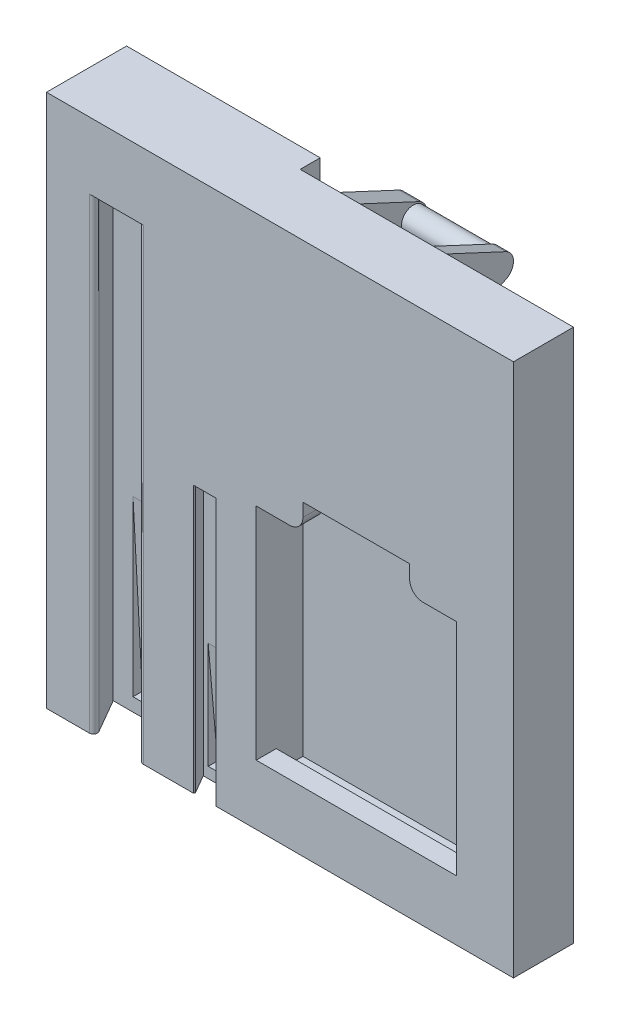
SolidWorks part; units mm, degrees
ref_plane "Front Plane" through (0, 0, 0) normal (0, 0, 1) x (1, 0, 0)
ref_plane "Top Plane" through (0, 0, 0) normal (0, 1, 0) x (1, 0, 0)
ref_plane "Right Plane" through (0, 0, 0) normal (1, 0, 0) x (0, 0, -1)
sketch "Sketch1" plane through (0, 0, 0) normal (0, 0, 1) x (1, 0, 0)
  line L0 (17.5, 20) -> (-17.5, -20) construction
  line L1 (-17.5, 20) -> (17.5, 20)
  line L2 (-17.5, 20) -> (-17.5, -20)
  line L3 (-17.5, -20) -> (17.5, -20)
  line L4 (17.5, 20) -> (17.5, -20)
  point P4 (0, 0)
  dimension "D1" = 40
  dimension "D2" = 35
extrude "Boss-Extrude1" add sketch "Sketch1" along normal blind 6
sketch "Sketch2" plane through (0, -20, 0) normal (0, -1, 0) x (1, 0, 0)
  line L0 (-10.7679, 6) -> (-9.0359, 3)
  line L1 (-17.5, 6) -> (17.5, 6) construction
  line L2 (-9.0359, 3) -> (-15.5, 3)
  line L3 (-15.5, 3) -> (-13.7679, 6)
  line L4 (-13.7679, 6) -> (-10.7679, 6)
  line L5 (-17.5, 6) -> (-17.5, 0) construction
  dimension "D1" = 3
  dimension "D2" = 60
  dimension "D3" = 3
  dimension "D4" = 2
extrude "Cut-Extrude1" cut sketch "Sketch2" against normal blind 35
sketch "Sketch3" plane through (0, 0, 3) normal (0, 0, 1) x (1, 0, 0)
  line L0 (-13.5179, -17.5) -> (-11.0179, -17.5) construction
  line L1 (-13.5179, -16.5) -> (-11.0179, -16.5)
  line L2 (-13.5179, -18.5) -> (-11.0179, -18.5)
  line L3 (-15.5, -20) -> (-9.0359, -20) construction
  arc A0 (-13.5179, -16.5) -> (-13.5179, -18.5) centre (-13.5179, -17.5) ccw
  arc A1 (-11.0179, -18.5) -> (-11.0179, -16.5) centre (-11.0179, -17.5) ccw
  point P2 (-12.2679, -17.5)
  point P9 (-12.2679, -20)
  dimension "D1" = 2
  dimension "D2" = 2.5
  dimension "D3" = 1.5
extrude "Cut-Extrude2" [suppressed] cut sketch "Sketch3" against normal blind 2
fillet "Fillet3" [suppressed] radius 1
fillet "Fillet4" radius 0.3 2 edges at (-10.7679, -2.5, 6) (-13.7679, -2.5, 6)
sketch "Sketch5" plane through (0, -20, 0) normal (0, -1, 0) x (1, 0, 0)
  line L0 (-4.8823, 6) -> (-4.0163, 4.5)
  line L1 (-4.0163, 4.5) -> (-7.2483, 4.5)
  line L2 (-7.2483, 4.5) -> (-6.3823, 6)
  line L3 (-6.3823, 6) -> (-4.8823, 6)
  line L4 (-10.2483, 6) -> (17.5, 6) construction
  dimension "D1" = 1.5
  dimension "D2" = 60
  dimension "D3" = 1.5
  dimension "D4" = 3
extrude "Cut-Extrude4" cut sketch "Sketch5" against normal blind 20
chamfer "Chamfer1" distance 0.1 distance2 0.1 2 edges at (-4.8823, -10, 6) (-6.3823, -10, 6)
sketch "Sketch6" plane through (0, 0, 4.5) normal (0, 0, 1) x (1, 0, 0)
  line L0 (-6.1323, -17.7) -> (-5.1323, -17.7) construction
  line L1 (-6.1323, -16.9) -> (-5.1323, -16.9)
  line L2 (-6.1323, -18.5) -> (-5.1323, -18.5)
  line L3 (-7.2483, -20) -> (-4.0163, -20) construction
  arc A0 (-6.1323, -16.9) -> (-6.1323, -18.5) centre (-6.1323, -17.7) ccw
  arc A1 (-5.1323, -18.5) -> (-5.1323, -16.9) centre (-5.1323, -17.7) ccw
  point P2 (-5.6323, -17.7)
  point P9 (-5.6323, -20)
  dimension "D1" = 0.8
  dimension "D2" = 1
  dimension "D3" = 1.5
extrude "Cut-Extrude5" [suppressed] cut sketch "Sketch6" against normal blind 1.5
sketch "Sketch7" plane through (0, -20, 0) normal (0, -1, 0) x (1, 0, 0)
  line L0 (2.5611, 6) -> (3.1384, 5)
  line L1 (3.1384, 5) -> (0.9837, 5)
  line L2 (0.9837, 5) -> (1.5611, 6)
  line L3 (1.5611, 6) -> (2.5611, 6)
  line L4 (-4.7823, 6) -> (17.5, 6) construction
  dimension "D1" = 1
  dimension "D2" = 60
  dimension "D3" = 5
  dimension "D4" = 1
extrude "Cut-Extrude6" [suppressed] cut sketch "Sketch7" against normal blind 20
sketch "Sketch8" [suppressed] plane through (0, 0, 5) normal (0, 0, 1) x (1, 0, 0)
  line L0 (7.0611, -19) -> (7.0611, -17.4891) construction
  line L1 (6.4111, -19) -> (7.7111, -19)
  line L2 (6.4111, -19) -> (6.4111, -16)
  line L3 (6.4111, -16) -> (7.7111, -16)
  line L4 (7.7111, -19) -> (7.7111, -16)
  line L5 (5.9837, -20) -> (8.1384, -20) construction
  point P9 (7.0611, -20)
  dimension "D1" = 1
  dimension "D2" = 3
  dimension "D3" = 1.3
extrude "Cut-Extrude7" [suppressed] cut sketch "Sketch8" against normal blind 0.5
sketch "Sketch10" plane through (0, -20, 0) normal (0, -1, 0) x (1, 0, 0)
  line L1 (17.5, 0) -> (-2.9878, 0)
  line L2 (17.5, 0) -> (17.5, 1.5)
  line L3 (17.5, 1.5) -> (-2.9878, 1.5)
  line L4 (-2.9878, 0) -> (-2.9878, 1.5)
  dimension "D1" = 1.5
extrude "Cut-Extrude8" cut sketch "Sketch10" against normal through all
ref_plane "Plane1" through (-12.2679, 0, 0) normal (1, 0, 0) x (0, 0, -1)
sketch "Sketch11" plane through (-12.2679, 0, 0) normal (1, 0, 0) x (0, 0, -1)
  line L0 (-3, -19) -> (-3, -6)
  line L1 (-3, 15) -> (-3, -20) construction
  line L2 (-3, -6) -> (-2.3, -19)
  line L3 (-2.3, -19) -> (-3, -19)
  line L4 (-6, -20) -> (0, -20) construction
  dimension "D1" = 1
  dimension "D2" = 0.7
  dimension "D3" = 13
  dimension "D4" = 3.082
extrude "Cut-Extrude9" cut sketch "Sketch11" against normal mid plane 3.5
ref_plane "Plane2" through (-5.6323, 0, 0) normal (1, 0, 0) x (0, 0, -1)
sketch "Sketch12" plane through (-5.6323, 0, 0) normal (1, 0, 0) x (0, 0, -1)
  line L0 (-4.5, -19.2) -> (-4.5, -11.199)
  line L1 (-4.5, 0) -> (-4.5, -20) construction
  line L2 (-4.5, -11.199) -> (-3.8, -19.2)
  line L3 (-3.8, -19.2) -> (-4.5, -19.2)
  line L4 (-3, -20) -> (-5.55, -20) construction
  dimension "D1" = 5
  dimension "D2" = 0.8
  dimension "D3" = 0.7
extrude "Cut-Extrude10" cut sketch "Sketch12" against normal mid plane 2.5
sketch "Sketch13" plane through (0, 0, 6) normal (0, 0, 1) x (1, 0, 0)
  line L0 (-4.7823, -20) -> (17.5, -20) construction
  line L1 (13.2177, -17) -> (-1.7823, -17)
  line L2 (13.2177, -17) -> (13.2177, 3)
  line L3 (13.2177, 3) -> (-1.7823, 3)
  line L4 (-1.7823, -17) -> (-1.7823, 3)
  line L5 (-4.7823, 0) -> (-4.7823, -20) construction
  dimension "D1" = 15
  dimension "D2" = 20
  dimension "D3" = 3
  dimension "D4" = 3
extrude "Cut-Extrude11" cut sketch "Sketch13" against normal blind 3.5
sketch "Sketch14" plane through (0, 0, 6) normal (0, 0, 1) x (1, 0, 0)
  line L0 (13.2177, -17) -> (13.2177, 3) construction
  line L1 (-1.7823, -17) -> (13.2177, -17)
  line L2 (-1.7823, -17) -> (-1.7823, -15.5)
  line L3 (-1.7823, -15.5) -> (13.2177, -15.5)
  line L4 (13.2177, -17) -> (13.2177, -15.5)
  line L6 (-1.7823, 3) -> (1.7177, 3)
  line L7 (-1.7823, 3) -> (-1.7823, 1)
  line L8 (-1.7823, 1) -> (1.7177, 1)
  line L9 (1.7177, 3) -> (1.7177, 1)
  line L10 (13.2177, 3) -> (9.7177, 3)
  line L11 (13.2177, 3) -> (13.2177, 1)
  line L12 (13.2177, 1) -> (9.7177, 1)
  line L13 (9.7177, 3) -> (9.7177, 1)
  dimension "D1" = 3.5
  dimension "D2" = 2
  dimension "D3" = 1.5
extrude "Boss-Extrude2" add sketch "Sketch14" against normal blind 1.5
fillet "Fillet5" radius 1 2 edges at (1.7177, 1, 5.25) (9.7177, 1, 5.25)
sketch "Sketch4" plane through (0, 0, 0) normal (0, 0, -1) x (-1, 0, 0)
  text T0 "60deg 3mm SPAN 3mm dEPTH 0.3FILLET" font "Century Gothic" height 1
sketch "Sketch15" plane through (0, 0, 0) normal (1, 0, 0) x (0, 0, -1)
  line L0 (-6, 20) -> (-1.5, 20) construction
  line L2 (2.5, -2.9686) -> (1.3741, -3.369) construction
  line L3 (-1.5, 0) -> (2.9226, -2.0623)
  line L4 (2.9226, -3.8749) -> (-1.5, -5.9372)
  line L5 (-15.2957, 7.0314) -> (5.2623, 7.0314) construction
  line L6 (-1.5, 0) -> (-1.5, -5.9372)
  line L7 (2.9226, -2.0623) -> (-1.5, 0)
  line L8 (-1.5, -5.9372) -> (2.9226, -3.8749)
  line L15 (2.5, 17.0314) -> (1.3741, 17.4318) construction
  line L16 (-1.5, 20) -> (2.9226, 17.9377)
  line L17 (2.9226, 16.1251) -> (-1.5, 14.0628)
  line L18 (-1.5, 14.0628) -> (-1.5, 20)
  line L19 (2.9226, 17.9377) -> (-1.5, 20)
  line L20 (-1.5, 14.0628) -> (2.9226, 16.1251)
  line L21 (-1.5, 20) -> (-1.5, -20) construction
  arc A0 (2.9226, -2.0623) -> (2.9226, -3.8749) centre (2.5, -2.9686) cw
  circle A1 centre (2.5, -2.9686) radius 0.9
  circle A4 centre (2.5, 17.0314) radius 0.9
  arc A5 (2.9226, 16.1251) -> (2.9226, 17.9377) centre (2.5, 17.0314) ccw
  dimension "D7" = 1
  dimension "D8" = 1.8
  dimension "D1" = 20
  dimension "D6" = 50
  dimension "D9" = 5
extrude "Boss-Extrude3" add sketch "Sketch15" along normal blind 1.5 contours L17 A5 L16 L18 A4 | A0 L3 L6 L4 A1 region at (0, -2.9686, -0.0965) region at (0, 17.0314, -0.0965)
extrude "Boss-Extrude4" add sketch "Sketch15<3>" along normal blind 1 from offset 7 contours A0 L3 L6 L4 A1 | L17 A5 L16 L18 A4 region at (0, -2.9686, -0.0965) region at (0, 17.0314, -0.0965)
sketch "Sketch15<3>" plane through (0, 0, 0) normal (1, 0, 0) x (0, 0, -1) same geometry as "Sketch15"
extrude "Boss-Extrude5" add sketch "Sketch15<4>" along normal up to surface (8 mm away) contours A4 | A1 region at (0, -2.9686, -2.5) region at (0, 17.0314, -2.5) up to face at (8, 17.0314, -3.4)
sketch "Sketch15<4>" plane through (0, 0, 0) normal (1, 0, 0) x (0, 0, -1) same geometry as "Sketch15"
